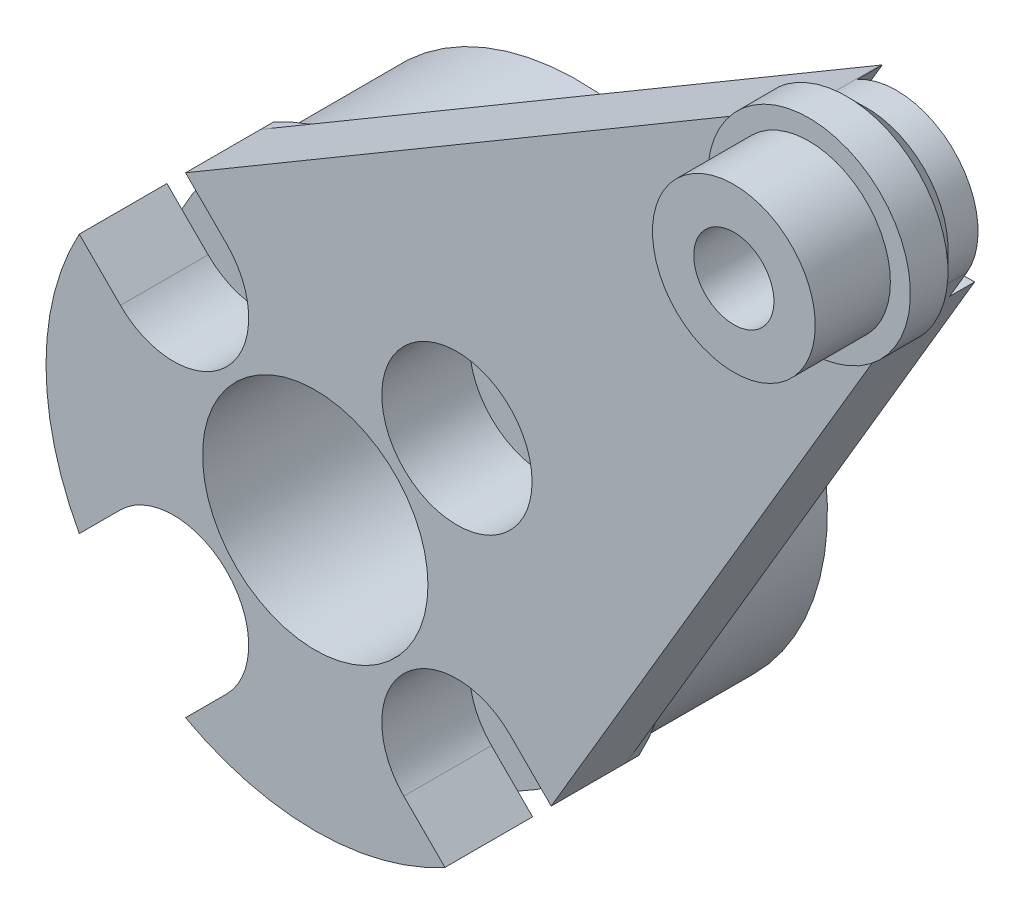
SolidWorks part; units mm, degrees
ref_plane "Front Plane" through (0, 0, 0) normal (0, 0, 1) x (1, 0, 0)
ref_plane "Top Plane" through (0, 0, 0) normal (0, 1, 0) x (1, 0, 0)
ref_plane "Right Plane" through (0, 0, 0) normal (1, 0, 0) x (0, 0, -1)
sketch "Sketch1" plane through (0, 0, 0) normal (0, 0, 1) x (1, 0, 0)
  line L0 (-7.0357, -7.0357) -> (-6.7882, -6.7882) construction
  circle A0 centre (0, 0) radius 9.95
  circle A1 centre (0, 0) radius 4.5
  circle A2 centre (-5.6569, -5.6569) radius 1.6
  circle A3 centre (-5.6569, 5.6569) radius 1.6
  circle A4 centre (5.6569, 5.6569) radius 1.6
  circle A5 centre (5.6569, -5.6569) radius 1.6
  point P18 (0, 0)
  dimension "D1" = 19.9
  dimension "D2" = 9
  dimension "D3" = 3.2
  dimension "D4" = 4
  dimension "D5" = 90
  dimension "D6" = 8
extrude "Boss-Extrude1" add sketch "Sketch1" against normal blind 7
sketch "Sketch3" plane through (0, 0, 0) normal (0, 0, 1) x (1, 0, 0)
  line L0 (-11.3137, 11.3137) -> (-5.6569, 5.6569) construction
  line L1 (-9.1924, 13.435) -> (-3.5355, 7.7782)
  line L2 (-13.435, 9.1924) -> (-7.7782, 3.5355)
  line L3 (11.3137, 11.3137) -> (5.6569, 5.6569) construction
  line L4 (13.435, 9.1924) -> (7.7782, 3.5355)
  line L5 (9.1924, 13.435) -> (3.5355, 7.7782)
  line L6 (11.3137, -11.3137) -> (5.6569, -5.6569) construction
  line L7 (9.1924, -13.435) -> (3.5355, -7.7782)
  line L8 (13.435, -9.1924) -> (7.7782, -3.5355)
  line L9 (-11.3137, -11.3137) -> (-5.6569, -5.6569) construction
  line L10 (-13.435, -9.1924) -> (-7.7782, -3.5355)
  line L11 (-9.1924, -13.435) -> (-3.5355, -7.7782)
  circle A0 centre (0, 0) radius 10.75
  circle A1 centre (0, 0) radius 9.95 construction
  arc A2 (-9.1924, 13.435) -> (-13.435, 9.1924) centre (-11.3137, 11.3137) ccw
  arc A3 (-7.7782, 3.5355) -> (-3.5355, 7.7782) centre (-5.6569, 5.6569) ccw
  arc A4 (13.435, 9.1924) -> (9.1924, 13.435) centre (11.3137, 11.3137) ccw
  arc A5 (3.5355, 7.7782) -> (7.7782, 3.5355) centre (5.6569, 5.6569) ccw
  arc A6 (9.1924, -13.435) -> (13.435, -9.1924) centre (11.3137, -11.3137) ccw
  arc A7 (7.7782, -3.5355) -> (3.5355, -7.7782) centre (5.6569, -5.6569) ccw
  arc A8 (-13.435, -9.1924) -> (-9.1924, -13.435) centre (-11.3137, -11.3137) ccw
  arc A9 (-3.5355, -7.7782) -> (-7.7782, -3.5355) centre (-5.6569, -5.6569) ccw
  point P8 (-8.4853, 8.4853)
  point P18 (8.4853, 8.4853)
  point P25 (8.4853, -8.4853)
  point P32 (-8.4853, -8.4853)
  point P37 (0, 0)
  circle M11 centre (0, 0) radius 4.5
  circle M12 centre (0, 0) radius 9.95
  dimension "D1" = 0.8
  dimension "D2" = 8
  dimension "D3" = 3
  dimension "D4" = 4
extrude "Boss-Extrude3" add sketch "Sketch3" along normal blind 0.5 contours A9 L11 L7 A7 L8 L4 A5 L5 L1 A3 L2 L10 M12 M11 | L2 A0 L10 M12 | L5 A0 L1 M12 | L8 A0 L4 M12 | L11 A0 L7 M12 region at (0, 10.6447, 0) region at (0, 9.6686, 0) region at (-9.1996, 4.8081, 0) region at (10.3104, 2.6468, 0) region at (-4.8081, -9.1996, 0)
sketch "Sketch5" plane through (0, 0, 0.5) normal (0, 0, 1) x (1, 0, 0)
  line L0 (21.2132, 21.2132) -> (0, 0) construction
  line L1 (-5.1781, 9.4207) -> (19.5621, 24.0126)
  line L3 (24.0126, 19.5621) -> (9.4207, -5.1781)
  line L8 (-3.5355, -7.7782) -> (-5.1781, -9.4207)
  line L9 (5.1781, -9.4207) -> (3.5355, -7.7782)
  line L10 (7.7782, -3.5355) -> (9.4207, -5.1781)
  line L11 (9.4207, 5.1781) -> (7.7782, 3.5355)
  line L12 (3.5355, 7.7782) -> (5.1781, 9.4207)
  line L13 (-5.1781, 9.4207) -> (-3.5355, 7.7782)
  line L14 (-7.7782, 3.5355) -> (-9.4207, 5.1781)
  line L15 (-9.4207, -5.1781) -> (-7.7782, -3.5355)
  line L16 (-3.5355, -7.7782) -> (-5.1781, -9.4207)
  line L17 (5.1781, -9.4207) -> (3.5355, -7.7782)
  line L18 (7.7782, -3.5355) -> (9.4207, -5.1781)
  line L21 (-5.1781, 9.4207) -> (-3.5355, 7.7782)
  line L22 (-7.7782, 3.5355) -> (-9.4207, 5.1781)
  line L23 (-9.4207, -5.1781) -> (-7.7782, -3.5355)
  circle A0 centre (5.6569, 5.6569) radius 3
  arc A1 (24.0126, 19.5621) -> (19.5621, 24.0126) centre (21.2132, 21.2132) ccw
  circle A2 centre (0, 0) radius 4.5 construction
  circle A3 centre (0, 0) radius 4.5
  arc A8 (-3.5355, -7.7782) -> (-7.7782, -3.5355) centre (-5.6569, -5.6569) ccw
  arc A9 (-5.1781, -9.4207) -> (5.1781, -9.4207) centre (0, 0) ccw
  arc A10 (7.7782, -3.5355) -> (3.5355, -7.7782) centre (5.6569, -5.6569) ccw
  arc A12 (3.5355, 7.7782) -> (7.7782, 3.5355) centre (5.6569, 5.6569) ccw
  arc A14 (-7.7782, 3.5355) -> (-3.5355, 7.7782) centre (-5.6569, 5.6569) ccw
  arc A15 (-5.1781, -9.4207) -> (5.1781, -9.4207) centre (0, 0) ccw
  arc A16 (-3.5355, -7.7782) -> (-7.7782, -3.5355) centre (-5.6569, -5.6569) ccw
  arc A18 (7.7782, -3.5355) -> (3.5355, -7.7782) centre (5.6569, -5.6569) ccw
  arc A22 (-7.7782, 3.5355) -> (-3.5355, 7.7782) centre (-5.6569, 5.6569) ccw
  arc A28 (9.4207, -5.1781) -> (9.4207, 5.1781) centre (0, 0) ccw
  arc A30 (5.1781, 9.4207) -> (-5.1781, 9.4207) centre (0, 0) ccw
  arc A32 (-9.4207, 5.1781) -> (-9.4207, -5.1781) centre (0, 0) ccw
  arc A33 (-9.4207, 5.1781) -> (-9.4207, -5.1781) centre (0, 0) ccw
  dimension "D3" = 3.25
  dimension "D2" = 30
  dimension "D1" = 0
extrude "Boss-Extrude4" add sketch "Sketch5" along normal blind 3
sketch "Sketch6" plane through (0, 0, 3.5) normal (0, 0, -1) x (-1, 0, 0)
  circle A0 centre (-21.2132, 21.2132) radius 3.25 construction
  circle A1 centre (-21.2132, 21.2132) radius 4.05
  dimension "D1" = 0.8
extrude "Boss-Extrude5" add sketch "Sketch6" against normal blind 1.5
sketch "Sketch7" plane through (0, 0, 5) normal (0, 0, 1) x (1, 0, 0)
  circle A0 centre (21.2132, 21.2132) radius 3.25
  circle A1 centre (21.2132, 21.2132) radius 4.05 construction
  dimension "D1" = 6.5
extrude "Boss-Extrude6" add sketch "Sketch7" along normal blind 3
chamfer "Chamfer1" distance 0.8 angle 45 3 edges at (23.3987, 18.5214, 3.5) (23.5113, 23.5113, 3.5) (18.5214, 23.3987, 3.5)
ref_axis "Axis1" through (21.2132, 21.2132, 8) along (0, 0, -1)
sketch "Sketch8" plane through (0, 0, 0.5) normal (0, 0, -1) x (-1, 0, 0)
  line L0 (-9.4207, -5.1781) -> (-24.0126, 19.5621) construction
  line L1 (-19.6227, 24.0281) -> (-22.8557, 23.9981) construction
  line L2 (-22.8557, 23.9981) -> (-24.4462, 21.1832) construction
  line L3 (-24.4462, 21.1832) -> (-22.8037, 18.3983) construction
  line L4 (-22.8037, 18.3983) -> (-19.5707, 18.4283)
  line L5 (-19.5707, 18.4283) -> (-17.9802, 21.2432)
  line L6 (-17.9802, 21.2432) -> (-19.6227, 24.0281)
  line L7 (-22.8037, 18.3983) -> (-23.3261, 18.3983)
  line L8 (-23.3261, 18.3983) -> (-24.0126, 19.5621)
  line L9 (-19.6227, 24.0281) -> (-19.6397, 24.0569)
  circle A0 centre (-21.2132, 21.2132) radius 2.8 construction
  arc A1 (-19.5621, 24.0126) -> (-24.0126, 19.5621) centre (-21.2132, 21.2132) ccw construction
  arc A3 (-19.6397, 24.0569) -> (-24.0126, 19.5621) centre (-21.2132, 21.2132) ccw
  dimension "D1" = 5.6
extrude "Cut-Extrude1" cut sketch "Sketch8" against normal blind 1
sketch "Sketch9" plane through (0, 0, 1.5) normal (0, 0, -1) x (-1, 0, 0)
  circle A0 centre (-21.2132, 21.2132) radius 1.6
  dimension "D1" = 3.2
extrude "Cut-Extrude2" cut sketch "Sketch9" against normal through all
sketch "Sketch10" plane through (0, 0, -7) normal (0, 0, -1) x (-1, 0, 0)
  line L0 (0, 0) -> (9.95, 0) construction
  arc A0 (9.6103, 2.5777) -> (9.6103, -2.5777) centre (9.95, 0) ccw
  circle A1 centre (0, 0) radius 9.95 construction
  arc A2 (9.6103, -2.5777) -> (9.6103, 2.5777) centre (0, 0) ccw
  dimension "D1" = 2.6
extrude "Boss-Extrude7" add sketch "Sketch10" along normal blind 2
sketch "Sketch11" plane through (0, 0, -7) normal (0, 0, -1) x (-1, 0, 0)
  line L0 (-3.1307, -4.8323) -> (-2.3807, -6.1313) construction
  line L1 (-2.2647, -4.3323) -> (-1.5147, -5.6313)
  line L2 (-3.9967, -5.3323) -> (-3.2467, -6.6313)
  line L3 (0, 0) -> (0, -9.95) construction
  arc A1 (-2.2647, -4.3323) -> (-3.9967, -5.3323) centre (-3.1307, -4.8323) ccw
  arc A2 (-3.2467, -6.6313) -> (-1.5147, -5.6313) centre (-2.3807, -6.1313) ccw
  circle A3 centre (-5.6569, -5.6569) radius 1.6 construction
  arc A4 (9.6103, 2.5777) -> (9.6103, -2.5777) centre (0, 0) ccw construction
  point P2 (-2.7557, -5.4818)
  point P9 (-2.0013, -6.7885)
  point P10 (-2.3263, -6.2255)
  point P13 (-3.2591, -4.6099)
  point P14 (0, -9.95)
  dimension "D1" = 2
  dimension "D2" = 30
  dimension "D3" = 1.5
  dimension "D4" = 4.5
extrude "Cut-Extrude3" cut sketch "Sketch11" against normal blind 2 draft 5
